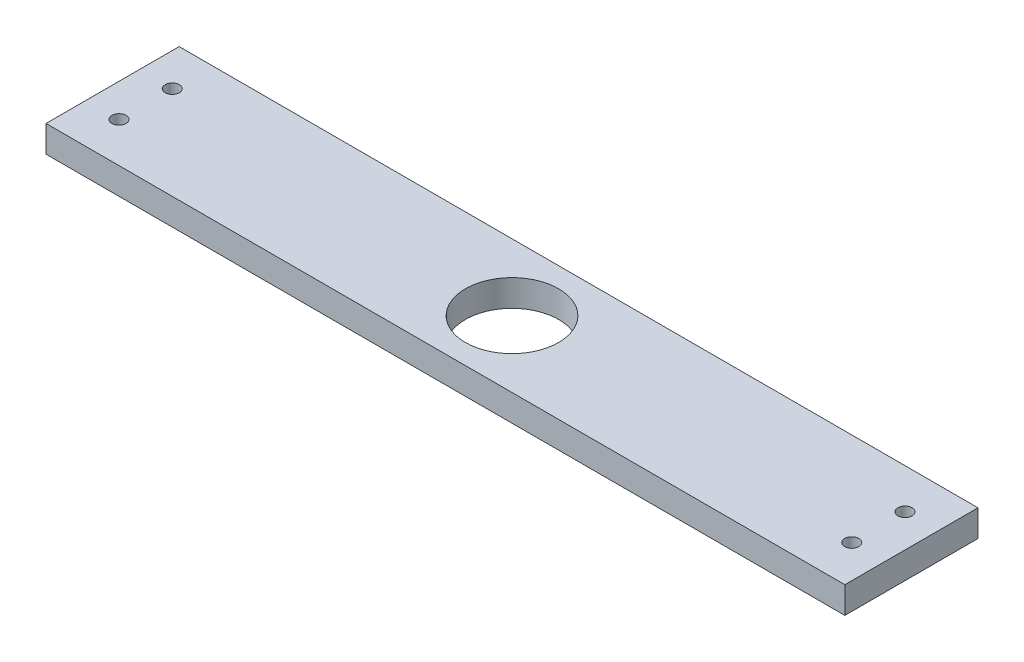
SolidWorks part; units mm, degrees
material "6061-T6 (SS)"
ref_plane "Front Plane" through (0, 0, 0) normal (0, 0, 1) x (1, 0, 0)
ref_plane "Top Plane" through (0, 0, 0) normal (0, 1, 0) x (1, 0, 0)
ref_plane "Right Plane" through (0, 0, 0) normal (1, 0, 0) x (0, 0, -1)
sketch "Sketch1" plane through (0, 0, 0) normal (0, 1, 0) x (1, 0, 0)
  line L1 (-190.5, -31.75) -> (190.5, -31.75)
  line L2 (-190.5, -31.75) -> (-190.5, 31.75)
  line L3 (-190.5, 31.75) -> (190.5, 31.75)
  line L4 (190.5, -31.75) -> (190.5, 31.75)
  line L5 (-190.5, -31.75) -> (190.5, 31.75) construction
  line L6 (-190.5, 31.75) -> (190.5, -31.75) construction
  point P0 (0, 0)
  dimension "D1" = 381
  dimension "D2" = 63.5
extrude "Boss-Extrude1" add sketch "Sketch1" along normal blind 12.7
sketch "Sketch2" plane through (0, 12.7, 0) normal (0, 1, 0) x (1, 0, 0)
  circle A0 centre (0, 0) radius 22.225
  dimension "D1" = 44.45
extrude "Cut-Extrude1" cut sketch "Sketch2" against normal through all
hole_wizard "1/4 Clearance Hole1" positions "Sketch4" profile "Sketch5" hole size "1/4" standard "ANSI Inch" end condition through all
sketch "Sketch4" plane through (0, 12.7, 0) normal (0, 1, 0) x (1, 0, 0)
  line L6 (-174.7388, -12.7) -> (-190.5, -31.75)
  line L9 (-174.7388, 12.7) -> (-190.5, 31.75)
  line L14 (190.5, 31.75) -> (174.7388, 12.7)
  line L17 (174.7388, -12.7) -> (190.5, -31.75)
  point P0 (-174.7388, 12.7)
  point P2 (174.7388, 12.7)
  point P24 (-174.7388, -12.7)
  point P26 (174.7388, -12.7)
  dimension "D1" = 349.4776
  dimension "D2" = 25.4
sketch "Sketch5" plane through (-174.7388, 12.7, -12.7) normal (1, 0, 0) x (0, 0, 1)
  line L0 (0, 0) -> (0, 12.7)
  line L1 (0, 12.7) -> (3.3782, 12.7)
  line L2 (3.3782, 12.7) -> (3.3782, 0)
  line L5 (3.3782, 0) -> (0, 0)
  line L11 (0, -6.35) -> (0, 107.95) construction
  dimension "Thru Hole Dia." = 6.7564
  dimension "Thru Hole Depth" = 12.7
